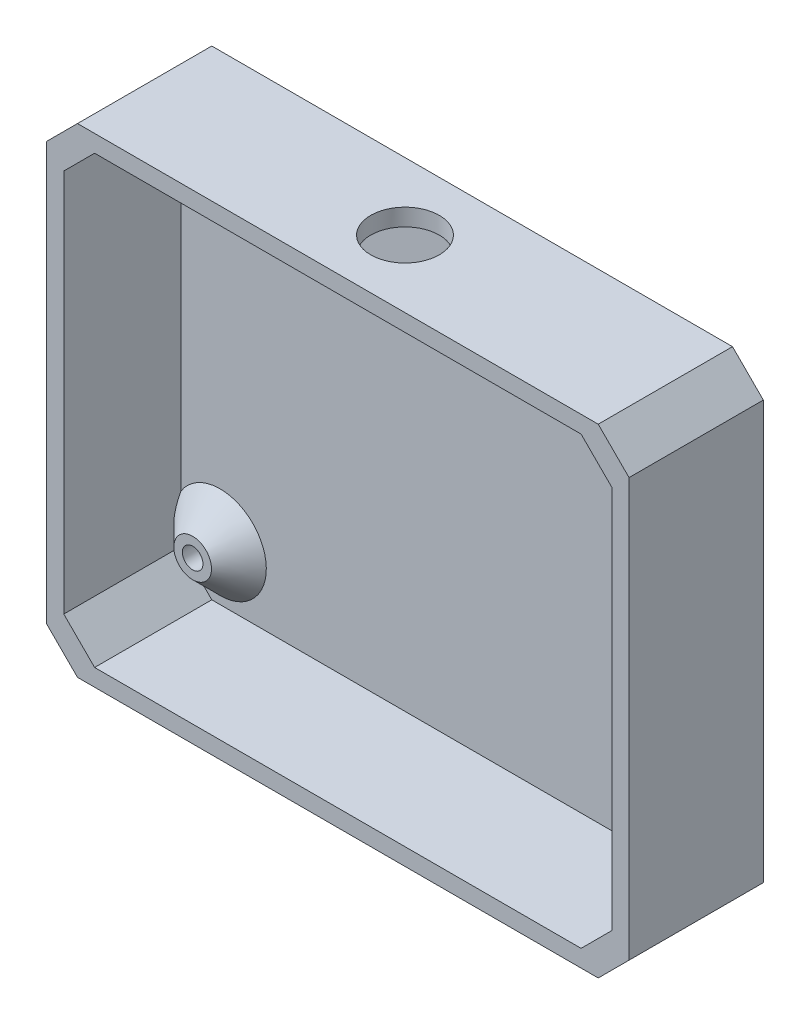
SolidWorks part; units mm, degrees
ref_plane "Plan de face" through (0, 0, 0) normal (0, 0, 1) x (1, 0, 0)
ref_plane "Plan de dessus" through (0, 0, 0) normal (0, 1, 0) x (1, 0, 0)
ref_plane "Plan de droite" through (0, 0, 0) normal (1, 0, 0) x (0, 0, -1)
sketch "Esquisse1" plane through (0, 0, 0) normal (0, 0, 1) x (1, 0, 0)
  line L1 (0, 0) -> (85, 0)
  line L2 (0, 0) -> (0, 70)
  line L3 (0, 70) -> (85, 70)
  line L4 (85, 0) -> (85, 70)
  dimension "D1" = 85
  dimension "D2" = 70
extrude "Boss.-Extru.1" add sketch "Esquisse1" along normal blind 2.5
sketch "Esquisse2" plane through (0, 0, 2.5) normal (0, 0, 1) x (1, 0, 0)
  line L8 (2.5, 67.5) -> (2.5, 2.5)
  line L9 (2.5, 2.5) -> (82.5, 2.5)
  line L10 (82.5, 2.5) -> (82.5, 67.5)
  line L11 (82.5, 67.5) -> (2.5, 67.5)
  line L12 (2.5, 67.5) -> (2.5, 2.5)
  line L13 (2.5, 2.5) -> (82.5, 2.5)
  line L14 (82.5, 2.5) -> (82.5, 67.5)
  line L15 (82.5, 67.5) -> (2.5, 67.5)
  line L16 (0, 70) -> (0, 0)
  line L17 (0, 0) -> (85, 0)
  line L18 (85, 0) -> (85, 70)
  line L19 (85, 70) -> (0, 70)
  line L20 (0, 70) -> (0, 0)
  line L21 (0, 0) -> (85, 0)
  line L22 (85, 0) -> (85, 70)
  line L23 (85, 70) -> (0, 70)
  dimension "D1" = 2.5
  dimension "D2" = 0
extrude "Boss.-Extru.2" add sketch "Esquisse2" along normal blind 17.1
sketch "Esquisse3" plane through (0, 0, 2.5) normal (0, 0, 1) x (1, 0, 0)
  line L0 (82.5, 67.5) -> (2.5, 67.5) construction
  line L1 (76.79, 10.39) -> (8.21, 10.39) construction
  line L2 (76.79, 10.39) -> (76.79, 61.19) construction
  line L3 (76.79, 61.19) -> (8.21, 61.19) construction
  line L4 (8.21, 10.39) -> (8.21, 61.19) construction
  line L5 (76.79, 10.39) -> (8.21, 61.19) construction
  line L6 (76.79, 61.19) -> (8.21, 10.39) construction
  line L10 (82.5, 67.5) -> (2.5, 67.5) construction
  line L11 (42.5, 67.5) -> (42.5, 2.5) construction
  line L12 (2.5, 2.5) -> (82.5, 2.5) construction
  line L13 (80.6, 6.58) -> (4.4, 6.58) construction
  line L14 (80.6, 6.58) -> (80.6, 65) construction
  line L15 (80.6, 65) -> (4.4, 65) construction
  line L16 (4.4, 6.58) -> (4.4, 65) construction
  line L17 (80.6, 6.58) -> (4.4, 65) construction
  line L18 (80.6, 65) -> (4.4, 6.58) construction
  circle A0 centre (8.21, 61.19) radius 1.5
  circle A1 centre (8.21, 61.19) radius 2.75
  circle A2 centre (76.79, 61.19) radius 1.5
  circle A3 centre (76.79, 61.19) radius 2.75
  circle A4 centre (76.79, 10.39) radius 2.75
  circle A5 centre (76.79, 10.39) radius 1.5
  circle A6 centre (8.21, 10.39) radius 2.75
  circle A7 centre (8.21, 10.39) radius 1.5
  point P0 (42.5, 35.79)
  point P26 (42.5, 35.79)
  dimension "D1" = 3
  dimension "D2" = 1.25
  dimension "D3" = 68.58
  dimension "D4" = 50.8
  dimension "D5" = 76.2
  dimension "D6" = 58.42
  dimension "D7" = 2.5
extrude "Boss.-Extru.3" add sketch "Esquisse3" along normal blind 4
chamfer "Chanfrein1" distance 4.5 angle 45 8 edges at (85, 0, 9.8) (82.5, 67.5, 11.05) (85, 70, 9.8) (0, 70, 9.8) (0, 0, 9.8) (82.5, 2.5, 11.05) (2.5, 2.5, 11.05) (2.5, 67.5, 11.05)
chamfer "Chanfrein2" distance 4 angle 45 4 edges at (5.46, 10.39, 2.5) (74.04, 10.39, 2.5) (74.04, 61.19, 2.5) (5.46, 61.19, 2.5)
sketch "Esquisse4" plane through (0, 70, 0) normal (0, 1, 0) x (1, 0, 0)
  line L0 (42.5, 0) -> (42.5, -19.6) construction
  line L1 (80.5, 0) -> (4.5, 0) construction
  line L2 (80.5, -19.6) -> (4.5, -19.6) construction
  circle A0 centre (42.5, -9.8) radius 5
  dimension "D1" = 10
extrude "Enlèv. mat.-Extru.1" cut sketch "Esquisse4" against normal blind 10 contours A0
equation "\"D1@Boss.-Extru.2\"=4+1.6+11.5"
